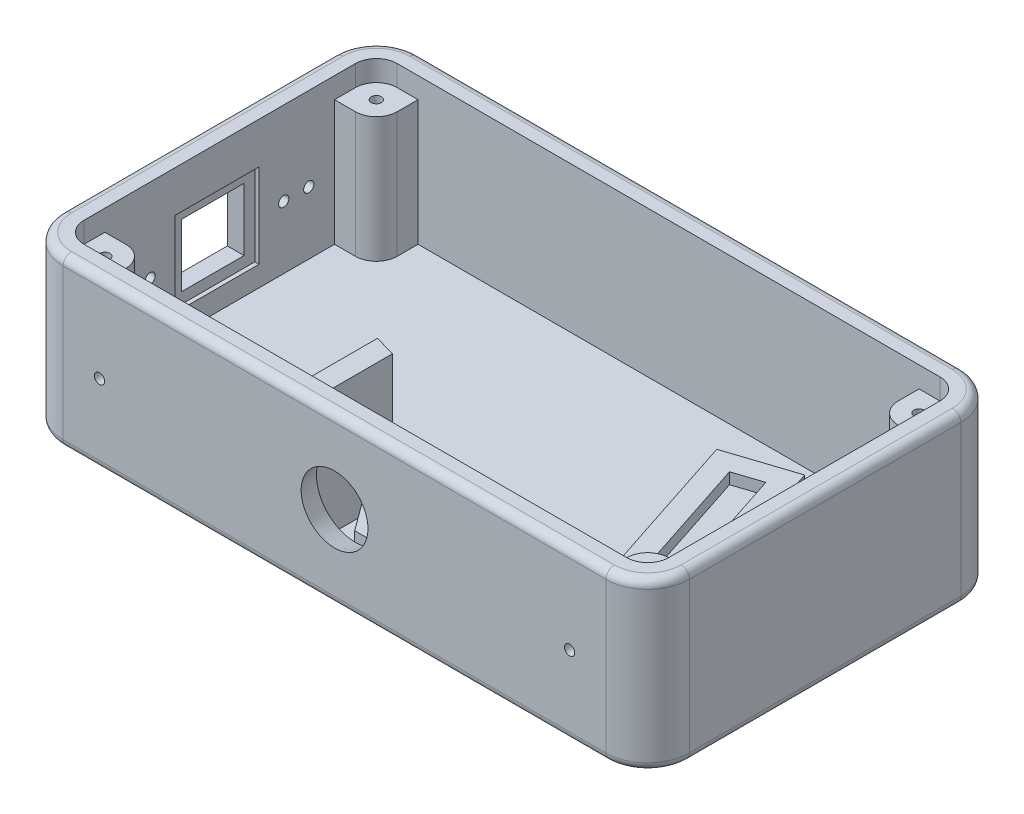
SolidWorks part; units mm, degrees
ref_plane "前视基准面" through (0, 0, 0) normal (0, 0, 1) x (1, 0, 0)
ref_plane "上视基准面" through (0, 0, 0) normal (0, 1, 0) x (1, 0, 0)
ref_plane "右视基准面" through (0, 0, 0) normal (1, 0, 0) x (0, 0, -1)
sketch "草图1" plane through (0, 0, 0) normal (0, 1, 0) x (1, 0, 0)
  line L0 (-65, -36.8238) -> (65, -36.8238)
  line L1 (31.2175, 23.7578) -> (46.7825, -23.7578) construction
  line L2 (35.9691, 25.3143) -> (51.534, -22.2013) construction
  line L3 (35.9691, 25.3143) -> (29.602, 23.2286) construction
  line L4 (29.602, 23.2286) -> (45.1669, -24.287) construction
  line L5 (51.534, -22.2013) -> (45.1669, -24.287) construction
  line L6 (0, -137.5901) -> (0, 34.855) construction
  line L7 (-5.9166, -20.5603) -> (5.9166, -36.684) construction
  line L8 (5.9166, -36.684) -> (7.529, -35.5007) construction
  line L9 (7.529, -35.5007) -> (-4.3042, -19.377) construction
  line L10 (-4.3042, -19.377) -> (-5.9166, -20.5603) construction
  line L11 (120.7724, 60.0129) -> (-26.0498, -47.7401) construction
  line L12 (181.8624, 46.7982) -> (-42.886, -26.8238) construction
  line L13 (-93.8575, 0) -> (197.9515, 0) construction
  line L14 (-71, 10) -> (-71, -10)
  line L15 (-70, 33.1762) -> (-70, -31.8238)
  line L16 (-65, 38.1762) -> (65, 38.1762)
  line L17 (70, 33.1762) -> (70, -31.8238)
  line L18 (70, 33.1762) -> (70, -31.8238)
  line L19 (-65, -36.8238) -> (65, -36.8238)
  line L20 (-70, 33.1762) -> (-70, -31.8238)
  line L21 (-65, 38.1762) -> (65, 38.1762)
  line L22 (-3.2316, -12.3877) -> (-10.3584, -17.6181)
  line L23 (-10.3584, -22.9588) -> (-0.1828, -36.8238)
  line L25 (14.5182, -36.5733) -> (-3.2316, -12.3877)
  line L26 (-4.2828, -19.2372) -> (-6.0564, -20.5388)
  line L27 (-6.0564, -20.5388) -> (5.8952, -36.8238)
  line L29 (7.6688, -35.5222) -> (-4.2828, -19.2372)
  line L30 (-12.9059, -19.4877) -> (4.844, -43.6733) construction
  line L31 (4.844, -43.6733) -> (14.5182, -36.5733) construction
  line L32 (14.5182, -36.5733) -> (14.7021, -36.8238)
  line L33 (39.1642, 31.6224) -> (23.294, 26.4237)
  line L34 (23.294, 26.4237) -> (41.9719, -30.5951)
  line L35 (57.8421, -25.3964) -> (41.9719, -30.5951)
  line L36 (39.1642, 31.6224) -> (57.8421, -25.3964)
  line L37 (36.033, 25.4405) -> (29.4758, 23.2925)
  line L38 (29.4758, 23.2925) -> (45.103, -24.4132)
  line L39 (51.6602, -22.2652) -> (45.103, -24.4132)
  line L40 (36.033, 25.4405) -> (51.6602, -22.2652)
  line L41 (75, 33.1762) -> (75, -31.8238)
  line L42 (-65, -41.8238) -> (65, -41.8238)
  line L43 (-75, 33.1762) -> (-75, -31.8238)
  line L44 (-65, 43.1762) -> (65, 43.1762)
  line L45 (-71, 10) -> (-70, 10)
  line L46 (-71, -10) -> (-70, -10)
  line L47 (-71, 0) -> (48.9552, -25.079) construction
  line L48 (-71, 0) -> (25.7263, -28.1017) construction
  line L49 (-10.3584, -17.6181) -> (-10.3584, -36.8238)
  line L50 (-3.2316, -12.3877) -> (-12.9059, -19.4877) construction
  line L51 (-10.3584, -17.6181) -> (-15.3584, -16.1654)
  line L52 (-15.3584, -16.1654) -> (-15.3584, -36.8238)
  line L53 (7.6688, -35.5222) -> (8.6241, -36.8238)
  line L54 (-70, 28.1762) -> (-65, 28.1762)
  line L55 (5.8952, -36.8238) -> (7.6688, -35.5222) construction
  line L56 (-60, 33.1762) -> (-60, 38.1762)
  line L57 (60, 38.1762) -> (60, 33.1762)
  line L58 (65, 28.1762) -> (70, 28.1762)
  line L59 (70, -26.8238) -> (65, -26.8238)
  line L60 (60, -31.8238) -> (60, -36.8238)
  line L61 (-70, -26.8238) -> (-65, -26.8238)
  line L62 (-60, -31.8238) -> (-60, -36.8238)
  arc A0 (-65, -36.8238) -> (-70, -31.8238) centre (-65, -31.8238) cw
  arc A1 (65, -36.8238) -> (70, -31.8238) centre (65, -31.8238) ccw
  arc A2 (65, 38.1762) -> (70, 33.1762) centre (65, 33.1762) cw
  arc A3 (-70, 33.1762) -> (-65, 38.1762) centre (-65, 33.1762) cw
  arc A4 (65, -36.8238) -> (70, -31.8238) centre (65, -31.8238) ccw
  arc A5 (-65, -36.8238) -> (-70, -31.8238) centre (-65, -31.8238) cw
  arc A6 (-70, 33.1762) -> (-65, 38.1762) centre (-65, 33.1762) cw
  arc A7 (65, 38.1762) -> (70, 33.1762) centre (65, 33.1762) cw
  arc A8 (65, -41.8238) -> (75, -31.8238) centre (65, -31.8238) ccw
  arc A9 (-65, -41.8238) -> (-75, -31.8238) centre (-65, -31.8238) cw
  arc A10 (-75, 33.1762) -> (-65, 43.1762) centre (-65, 33.1762) cw
  arc A11 (65, 43.1762) -> (75, 33.1762) centre (65, 33.1762) cw
  arc A12 (65, -26.8238) -> (60, -31.8238) centre (65, -31.8238) ccw
  arc A13 (60, 33.1762) -> (65, 28.1762) centre (65, 33.1762) ccw
  arc A14 (-65, -26.8238) -> (-60, -31.8238) centre (-65, -31.8238) cw
  arc A15 (-65, 28.1762) -> (-60, 33.1762) centre (-65, 33.1762) ccw
  circle A16 centre (-65, 33.1762) radius 1.225
  circle A17 centre (-65, -31.8238) radius 1.225
  circle A18 centre (65, -31.8238) radius 1.225
  circle A19 centre (65, 33.1762) radius 1.225
  point P10 (0, -36.8238)
  point P14 (0, -28.6222)
  point P21 (39, 0)
  point P29 (-71, 0)
  point P30 (-70, -36.8238)
  point P34 (70, -36.8238)
  point P39 (-70, 38.1762)
  point P118 (-70, 0)
  dimension "D13" = 5
  dimension "D14" = 5
  dimension "D24" = 5
  dimension "D25" = 2.45
  dimension "D1" = 140
  dimension "D2" = 6.7
  dimension "D3" = 50
  dimension "D4" = 5
  dimension "D5" = 20
  dimension "D6" = 2
  dimension "D7" = 53.725
  dimension "D8" = 18.138
  dimension "D9" = 110
  dimension "D10" = 1
  dimension "D11" = 20
  dimension "D12" = 75
  dimension "D21" = 5
  dimension "D22" = 10
  dimension "D23" = 10
  dimension "D26" = 28.1762
  dimension "D15" = 0
  dimension "D16" = 5
  dimension "D17" = 0.1
  dimension "D18" = 5
  dimension "D19" = 0.1
  dimension "D20" = 5
extrude "凸台-拉伸1" add sketch "草图1" along normal blind 5 contours L43 A9 L42 A8 L41 A11 L44 A10
extrude "凸台-拉伸3" add sketch "草图1<5>" along normal blind 10 contours L36 L33 L34 L35 L37 L40 L39 L38 region at (47.8268, 0, -2.8914)
sketch "草图1<5>" plane through (0, 0, 0) normal (0, 1, 0) x (1, 0, 0) same geometry as "草图1"
extrude "凸台-拉伸6" add sketch "草图1<7>" along normal blind 35 contours L51 L52 L19 L49 region at (-12.8887, 0, 26.8534)
sketch "草图1<7>" plane through (0, 0, 0) normal (0, 1, 0) x (1, 0, 0) same geometry as "草图1"
extrude "凸台-拉伸7" add sketch "草图1<8>" along normal blind 40 contours A11 L44 A10 L43 A9 L42 A8 L41 L15 A3 L16 A2 L17 A1 L19 L0 A0 L46 L14 L45 region at (73.2759, 0, -0.6762)
sketch "草图1<8>" plane through (0, 0, 0) normal (0, 1, 0) x (1, 0, 0) same geometry as "草图1"
extrude "凸台-拉伸8" add sketch "草图1<11>" along normal blind 13 contours L29 L53 L19 L32 L25 L22 L49 L23 L27 L26 region at (-4.9884, 0, 29.6842)
sketch "草图1<11>" plane through (0, 0, 0) normal (0, 1, 0) x (1, 0, 0) same geometry as "草图1"
extrude "凸台-拉伸9" add sketch "草图1<12>" along normal blind 40 contours L14 L46 L20 L45 region at (-70.5, 0, 0)
sketch "草图1<12>" plane through (0, 0, 0) normal (0, 1, 0) x (1, 0, 0) same geometry as "草图1"
sketch "草图3" plane through (0, 0, 41.8238) normal (0, 0, 1) x (1, 0, 0)
  line L0 (-39.0257, 20) -> (36.1639, 20) construction
  line L1 (0, 36.1869) -> (0, 3.9069) construction
  line L2 (-65, 0) -> (65, 0) construction
  line L3 (-57.9765, 19) -> (59.4964, 19) construction
  circle A0 centre (0, 20) radius 8
  circle A1 centre (56.3, 19) radius 1.225
  circle A2 centre (-56.3, 19) radius 1.225
  point P6 (0, 0)
  point P9 (0, 20)
  dimension "D2" = 16
  dimension "D4" = 2.45
  dimension "D1" = 20
  dimension "D3" = 1
  dimension "D5" = 56.3
  dimension "D6" = 56.3
extrude "切除-拉伸2" cut sketch "草图3" against normal blind 5 draft 15 contours A0 region at (0, 20, 41.8238) draft outward yes
extrude "切除-拉伸3" cut sketch "草图3<3>" against normal blind 5 contours A1 | A2
sketch "草图3<3>" plane through (0, 0, 41.8238) normal (0, 0, 1) x (1, 0, 0) same geometry as "草图3"
extrude "凸台-拉伸10" add sketch "草图1<13>" along normal blind 7.3 contours L40 L39 L38 L37
sketch "草图1<13>" plane through (0, 0, 0) normal (0, 1, 0) x (1, 0, 0) same geometry as "草图1"
extrude "凸台-拉伸11" add sketch "草图1<16>" along normal blind 10 contours L53 L29 L26 L27 L0 region at (1.0594, 0, 28.3517)
sketch "草图1<16>" plane through (0, 0, 0) normal (0, 1, 0) x (1, 0, 0) same geometry as "草图1"
extrude "凸台-拉伸12" add sketch "草图1<17>" along normal blind 35 contours L54 A15 L56 L16 A3 L15 | A14 L61 L20 A0 L0 L62 | L57 A13 L58 L17 A2 L16 | L59 A12 L60 L0 A1 L17 region at (-68.4355, 0, 35.2593) region at (-69.8586, 0, -30.6762) region at (60.1414, 0, 34.3238) region at (62.5, 0, -38.0348)
sketch "草图1<17>" plane through (0, 0, 0) normal (0, 1, 0) x (1, 0, 0) same geometry as "草图1"
sketch "草图4" plane through (-70, 0, 0) normal (1, 0, 0) x (0, 0, -1)
  line L0 (33.1762, 0) -> (-31.8238, 0) construction
  line L1 (-10, 30) -> (10, 30) construction
  line L2 (-10, 30) -> (-10, 10) construction
  line L3 (-10, 10) -> (10, 10) construction
  line L4 (10, 30) -> (10, 10) construction
  line L30 (-7.5, 27.5) -> (7.5, 27.5)
  line L31 (-7.5, 27.5) -> (-7.5, 12.5)
  line L32 (-7.5, 12.5) -> (7.5, 12.5)
  line L33 (7.5, 27.5) -> (7.5, 12.5)
  line L37 (-10.1, 30.1) -> (10.1, 30.1)
  line L38 (10.1, 30.1) -> (10.1, 9.9)
  line L39 (-10.1, 9.9) -> (10.1, 9.9)
  line L40 (-10.1, 30.1) -> (-10.1, 9.9)
  line L41 (-26.8238, 5) -> (28.1762, 5)
  line L42 (28.1762, 5) -> (28.1762, 35)
  line L43 (28.1762, 35) -> (-26.8238, 35)
  line L44 (-26.8238, 35) -> (-26.8238, 5)
  line L45 (-26.8238, 5) -> (28.1762, 5)
  line L46 (28.1762, 5) -> (28.1762, 35)
  line L47 (28.1762, 35) -> (-26.8238, 35)
  line L48 (-26.8238, 35) -> (-26.8238, 5)
  line L49 (-29.8378, 20) -> (19.495, 20) construction
  line L50 (0, 33.8677) -> (0, 5.7357) construction
  circle A0 centre (-22, 20) radius 1.225
  circle A1 centre (22, 20) radius 1.225
  circle A2 centre (-16, 20) radius 1.225
  circle A3 centre (16, 20) radius 1.225
  point P25 (-7.5, 20)
  point P26 (0, 27.5)
  dimension "D10" = 2.45
  dimension "D1" = 20
  dimension "D2" = 10
  dimension "D4" = 15
  dimension "D5" = 2.5
  dimension "D6" = 2.5
  dimension "D9" = 6
  dimension "D11" = 6
  dimension "D12" = 12
  dimension "D13" = 12
  dimension "D7" = 5
  dimension "D8" = 0.1
extrude "切除-拉伸4" cut sketch "草图4" against normal blind 1 contours L37 L40 L39 L38 L30 L33 L32 L31 region at (-70, 29.8143, 0)
extrude "切除-拉伸5" cut sketch "草图4<2>" against normal blind 5 contours L33 L30 L31 L32 region at (-70, 20, 0)
sketch "草图4<2>" plane through (-70, 0, 0) normal (1, 0, 0) x (0, 0, -1) same geometry as "草图4"
extrude "切除-拉伸6" cut sketch "草图4<4>" against normal blind 5 contours A2 | A0 | A3 | A1 region at (-70, 20, 22) region at (-70, 20, -22) region at (-70, 20, 16) region at (-70, 20, -16)
sketch "草图4<4>" plane through (-70, 0, 0) normal (1, 0, 0) x (0, 0, -1) same geometry as "草图4"
fillet "圆角1" radius 2 8 edges at (72.0711, 40, -40.2473) (72.0711, 40, 38.8949) (-72.0711, 40, -40.2473) (-72.0711, 40, 38.8949) (75, 40, -0.6762) (0, 40, -43.1762) (-75, 40, -0.6762) (0, 40, 41.8238)
fillet "圆角2" radius 2 8 edges at (-72.0711, 0, 38.8949) (-75, 0, -0.6762) (-72.0711, 0, -40.2473) (0, 0, -43.1762) (72.0711, 0, -40.2473) (75, 0, -0.6762) (72.0711, 0, 38.8949) (0, 0, 41.8238)
